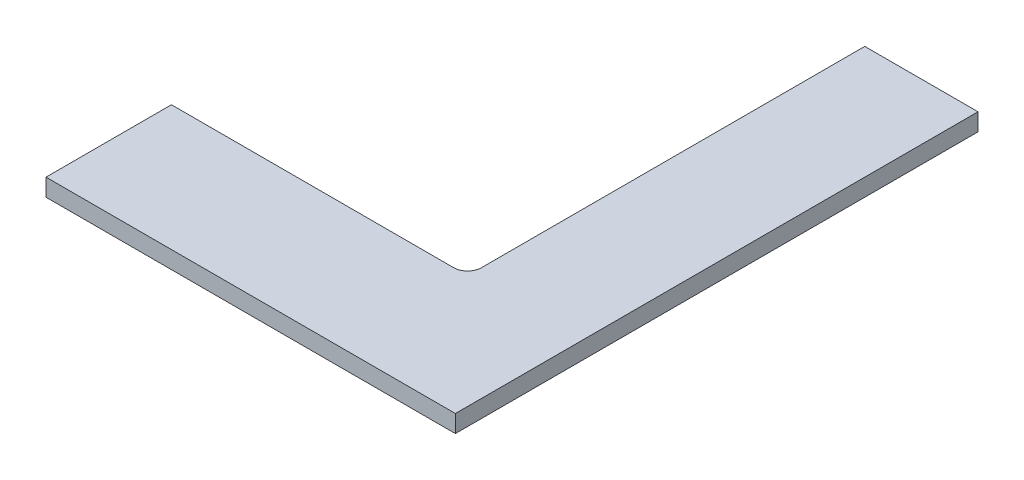
SolidWorks part; units mm, degrees
ref_plane "前视基准面" through (0, 0, 0) normal (0, 0, 1) x (1, 0, 0)
ref_plane "上视基准面" through (0, 0, 0) normal (0, 1, 0) x (1, 0, 0)
ref_plane "右视基准面" through (0, 0, 0) normal (1, 0, 0) x (0, 0, -1)
sketch "草图1" plane through (0, 0, 0) normal (0, 1, 0) x (1, 0, 0)
  line L1 (0, 0) -> (65, 0)
  line L2 (0, 0) -> (0, -300)
  line L3 (0, -300) -> (65, -300)
  line L4 (65, 0) -> (65, -300)
  dimension "D1" = 65
  dimension "D2" = 300
extrude "凸台-拉伸1" add sketch "草图1" along normal blind 10
sketch "草图2" plane through (0, 0, 0) normal (-1, 0, 0) x (0, 0, 1)
  line L0 (0, 10) -> (300, 10) construction
  line L1 (300, 0) -> (228, 0)
  line L2 (300, 0) -> (300, 10)
  line L3 (300, 10) -> (228, 10)
  line L4 (228, 0) -> (228, 10)
  dimension "D1" = 72
extrude "凸台-拉伸2" add sketch "草图2" along normal blind 170
fillet "圆角8" radius 8 1 edges at (0, 5, 228)
